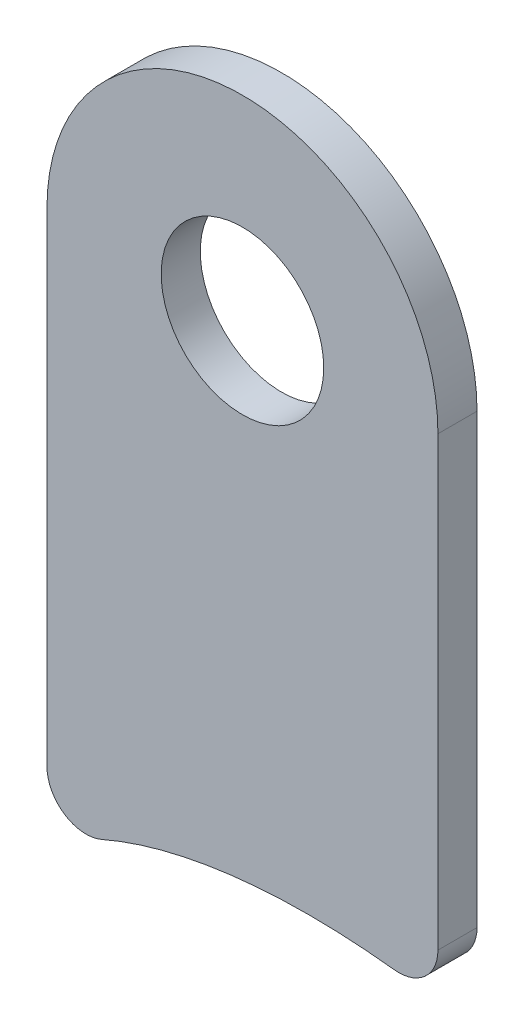
SolidWorks part; units mm, degrees
material "ASTM A36 Steel"
ref_plane "X-Y Datum" through (0, 0, 0) normal (0, 0, 1) x (1, 0, 0)
ref_plane "X-Z Datum" through (0, 0, 0) normal (0, 1, 0) x (1, 0, 0)
ref_plane "Y-Z Datum" through (0, 0, 0) normal (1, 0, 0) x (0, 0, -1)
sketch "Sketch1" plane through (0, 0, 0) normal (0, 0, 1) x (1, 0, 0)
  line L0 (-7.9375, 0) -> (-7.9375, -28.575)
  line L1 (-7.9375, -28.575) -> (7.9375, -28.575)
  line L2 (7.9375, -28.575) -> (7.9375, 0)
  circle A0 centre (0, 0) radius 7.9375
  circle A1 centre (0, 0) radius 3
  dimension "D1" = 6
  dimension "D2" = 15.875
  dimension "D3" = 28.575
extrude "Boss-Extrude1" add sketch "Sketch1" along normal blind 1.5875 contours A0 A1 | A0 L0 L1 L2 | A1 region at (0, -17.3343, 0) region at (0, 7.713, 0) region at (0, 0, 0)
hole_wizard "M6 Clearance Hole1" positions "Sketch2" profile "Sketch3" hole size "M6" standard "ANSI Metric" end condition through all
sketch "Sketch2" plane through (0, 0, 1.5875) normal (0, 0, 1) x (1, 0, 0)
  point P0 (0, 0)
sketch "Sketch3" plane through (0, 0, 1.5875) normal (1, 0, 0) x (0, -1, 0)
  line L0 (0, 0) -> (0, 1.5875)
  line L1 (0, 1.5875) -> (3.3, 1.5875)
  line L2 (3.3, 1.5875) -> (3.3, 0)
  line L5 (3.3, 0) -> (0, 0)
  line L11 (0, -6.35) -> (0, 107.95) construction
  dimension "Thru Hole Dia." = 6.6
  dimension "Thru Hole Depth" = 1.5875
sketch "Sketch4" [suppressed] plane through (0, 0, 1.5875) normal (0, 0, 1) x (1, 0, 0)
  line L1 (3.1668, -19.7964) -> (-108.0076, 158.4881) construction
  line L2 (3.1668, -19.7964) -> (-108.0076, 158.4881) construction
  line L3 (55.1899, 89.5082) -> (-10.3661, -44.0945) construction
  line L4 (55.1899, 89.5082) -> (-10.3661, -44.0945) construction
  line L5 (4.6946, -30.7509) -> (-111.826, 156.107)
  line L6 (59.2298, 87.526) -> (-6.3262, -46.0767)
  line L7 (-0.6516, -22.1775) -> (-111.826, 156.107) construction
  dimension "D1" = 4.5
extrude "Cut-Extrude1" [suppressed] cut sketch "Sketch4" against normal through all
sketch "Sketch5" plane through (0, 0, 1.5875) normal (0, 0, 1) x (1, 0, 0)
  line L0 (-7.9375, 0) -> (-7.9375, -28.575) construction
  line L1 (7.9375, -28.575) -> (-7.9375, -28.575)
  line L2 (7.9375, -28.575) -> (7.9375, -22.225)
  line L3 (7.9375, -22.225) -> (-7.9375, -22.225)
  line L4 (-7.9375, -28.575) -> (-7.9375, -22.225)
  dimension "D1" = 6.35
extrude "Cut-Extrude2" [suppressed] cut sketch "Sketch5" against normal through all
sketch "Sketch6" plane through (0, 0, 0) normal (0, 0, -1) x (-1, 0, 0)
  spline S0 degree 3 poles (11.1636, -26.4867) (3.0884, -2.4046) (-38.3742, -16.3077) (-30.299, -40.3899) (-22.2238, -64.4721) (19.2388, -50.5689) (11.1636, -26.4867) (3.0884, -2.4046) (-38.3742, -16.3077) knots -0.5 0 0 0 0.5 0.5 0.5 1 1 1 1.5 1.5 1.5 weights 1 0.333333 0.333333 1 0.333333 0.333333 1 0.333333 0.333333 only from (11.1636, -26.4867) to (11.1636, -26.4867)
  spline S1 degree 3 poles (11.1636, -26.4867) (3.0884, -2.4046) (-38.3742, -16.3077) (-30.299, -40.3899) (-22.2238, -64.4721) (19.2388, -50.5689) (11.1636, -26.4867) (3.0884, -2.4046) (-38.3742, -16.3077) knots -0.5 0 0 0 0.5 0.5 0.5 1 1 1 1.5 1.5 1.5 weights 1 0.333333 0.333333 1 0.333333 0.333333 1 0.333333 0.333333 only from (11.1636, -26.4867) to (11.1636, -26.4867)
extrude "Cut-Extrude3" cut sketch "Sketch6" against normal through all
fillet "Fillet1" [suppressed] radius 1.5875
fillet "Fillet2" radius 1.5875 2 edges at (-7.9375, -22.3342, 0.7937) (7.9375, -19.9806, 0.7937)
fillet "Fillet3" [suppressed] radius 1.5875
